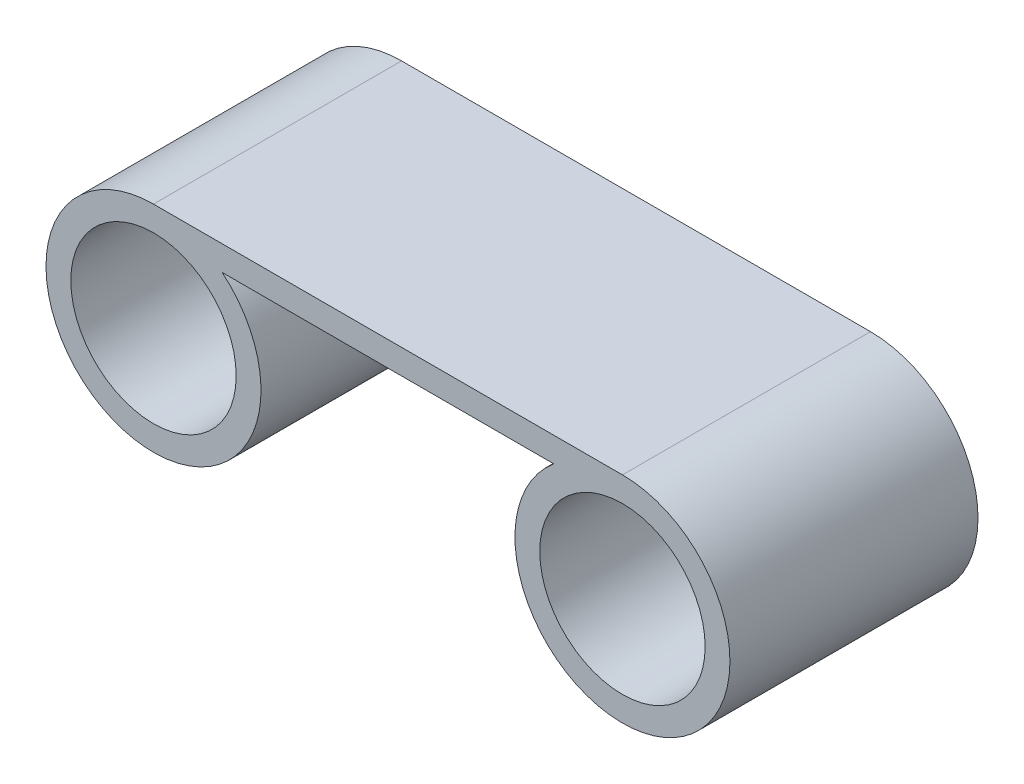
SolidWorks part; units mm, degrees
ref_plane "Front Plane" through (0, 0, 0) normal (0, 0, 1) x (1, 0, 0)
ref_plane "Top Plane" through (0, 0, 0) normal (0, 1, 0) x (1, 0, 0)
ref_plane "Right Plane" through (0, 0, 0) normal (1, 0, 0) x (0, 0, -1)
sketch "Sketch2" plane through (0, 0, 0) normal (0, 0, 1) x (1, 0, 0)
  line L5 (-28.3567, 0) -> (28.3567, 0)
  line L7 (-20.0501, -3) -> (20.0501, -3)
  arc A13 (-28.3567, 0) -> (-20.0501, -3) centre (-28.3567, -13) ccw
  arc A14 (20.0501, -3) -> (28.3567, 0) centre (28.3567, -13) ccw
  circle A15 centre (-28.3567, -13) radius 10
  circle A16 centre (28.3567, -13) radius 10
  point P3 (0, 0)
  dimension "D1" = 13
  dimension "D2" = 20
  dimension "D3" = 40.1003
  dimension "D4" = 20
  dimension "D5" = 13
  dimension "D6" = 3
extrude "Boss-Extrude1" add sketch "Sketch2" along normal blind 30
sketch "Sketch5" plane through (0, 0, 30) normal (0, 0, 1) x (1, 0, 0)
  line L1 (0, -12.4768) -> (30.8403, -12.4768) construction
  line L2 (0, 0) -> (0, -23.7204) construction
  line L3 (28.3567, 0) -> (-28.3567, 0) construction
  line L4 (0, -12.4768) -> (-29.0576, -12.4768) construction
  line L5 (-5.5848, -3) -> (5.5848, -3) construction
  line L6 (-20.0501, -3) -> (20.0501, -3) construction
  circle A2 centre (0, -12.4768) radius 4
  circle A8 centre (0, -12.4768) radius 7 construction
  circle A9 centre (-7, -12.4768) radius 1.75
  circle A10 centre (0, -19.4768) radius 1.75
  circle A11 centre (7, -12.4768) radius 1.75
  circle A12 centre (0, -5.4768) radius 1.75
  arc A14 (-5.5848, -3) -> (5.5848, -3) centre (0, -12.4768) ccw
  dimension "D4" = 3.5
  dimension "D5" = 14
  dimension "D6" = 3.5
  dimension "D7" = 3.5
  dimension "D8" = 3.5
  dimension "D9" = 8
extrude "Boss-Extrude2" add sketch "Sketch5" against normal blind 4 rebuild error yes
sketch "Sketch6" plane through (0, 0, 0) normal (0, 1, 0) x (1, 0, 0)
  line L0 (0, 0) -> (0, -30) construction
  line L1 (28.3567, -30) -> (-28.3567, -30) construction
  line L2 (-28.3567, -15) -> (28.3567, -15) construction
  line L3 (-28.3567, -30) -> (-28.3567, 0) construction
  line L4 (28.3567, -30) -> (28.3567, 0) construction
  circle A0 centre (-13.0346, -15) radius 3
  circle A1 centre (15.3466, -15) radius 3
extrude "Cut-Extrude1" [suppressed] cut sketch "Sketch6" against normal blind 4
